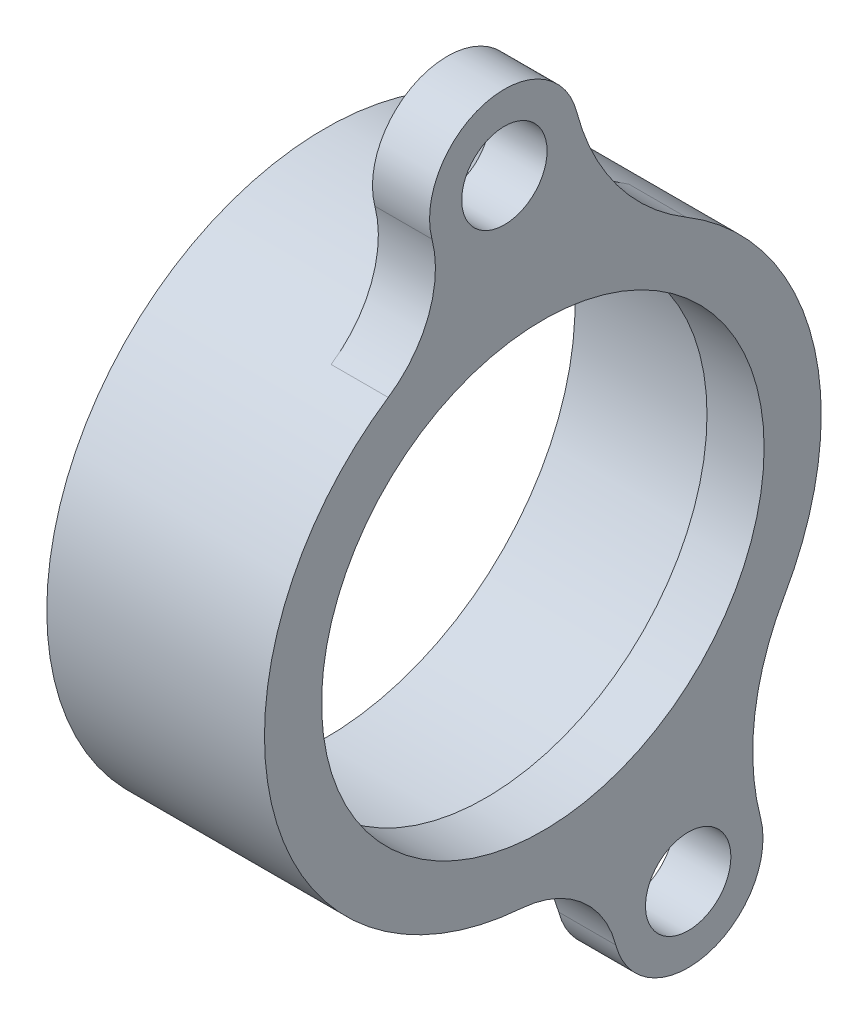
SolidWorks part; units mm, degrees
ref_plane "Front Plane" through (0, 0, 0) normal (0, 0, 1) x (1, 0, 0)
ref_plane "Top Plane" through (0, 0, 0) normal (0, 1, 0) x (1, 0, 0)
ref_plane "Right Plane" through (0, 0, 0) normal (1, 0, 0) x (0, 0, -1)
sketch "Sketch1" plane through (0, 0, 0) normal (0, 0, 1) x (1, 0, 0)
  line L0 (30.9563, 12.3825) -> (38.1, 12.3825)
  line L1 (38.1, 12.3825) -> (38.1, 11.1125)
  line L2 (38.1, 11.1125) -> (30.9563, 11.1125)
  line L4 (30.9563, 11.1125) -> (30.9563, 12.3825)
  line L5 (0, 0) -> (40.0174, 0) construction
  dimension "D1" = 1.27
  dimension "D2" = 7.1437
revolve "Revolve1" add sketch "Sketch1" angle 360 about L5
sketch "Sketch2" plane through (38.1, 0, 0) normal (1, 0, 0) x (0, 0, -1)
  line L0 (7.5709, -19.2497) -> (-3.6897, 23.8296) construction
  line L1 (-4.9307, 15.4199) -> (1.5078, 17.1029) construction
  line L2 (-11.2501, -2.9407) -> (11.2501, 2.9407) construction
  line L4 (-2.9246, 11.8422) -> (1.5091, 13.0012) construction
  line L5 (1.5091, 13.0012) -> (2.7223, 17.4204) construction
  line L6 (2.7223, 17.4204) -> (-0.4983, 20.6807) construction
  line L7 (-0.4983, 20.6807) -> (-4.932, 19.5217) construction
  line L8 (-4.932, 19.5217) -> (-6.1452, 15.1025) construction
  line L9 (-6.1452, 15.1025) -> (-2.9246, 11.8422) construction
  arc A0 (-6.8773, 10.297) -> (-0.9588, -12.3453) centre (0, 0) ccw
  circle A1 centre (0, 0) radius 12.3825 construction
  arc A7 (1.5078, 17.1029) -> (-4.9307, 15.4199) centre (-1.7114, 16.2614) ccw
  arc A8 (-6.8773, 10.297) -> (-4.9307, 15.4199) centre (-9.501, 14.2253) ccw
  arc A9 (1.5078, 17.1029) -> (6.3668, 10.6202) centre (11.8783, 19.8137) ccw
  circle A10 centre (0, 0) radius 9.8425
  circle A11 centre (0, 0) radius 11.1125 construction
  arc A12 (9.6843, -14.1774) -> (10.7495, -6.1462) centre (20.0548, -11.4666) cw
  arc A14 (9.6843, -14.1774) -> (3.2458, -15.8604) centre (6.465, -15.0189) cw
  arc A15 (-0.9588, -12.3453) -> (3.2458, -15.8604) centre (-1.3245, -17.055) cw
  arc A16 (10.7495, -6.1462) -> (6.3668, 10.6202) centre (0, 0) ccw
  circle A17 centre (-1.7114, 16.2614) radius 3.9688 construction
  arc A18 (1.5403, 20.0021) -> (-7.5172, 18.5996) centre (-2.9885, 19.3009) ccw construction
  arc A19 (7.5318, -19.9007) -> (7.5172, -18.5996) centre (2.9885, -19.3009) ccw construction
  dimension "D1" = 1.27
  dimension "D2" = 3.3274
  dimension "D3" = 7.9375
extrude "Boss-Extrude1" add sketch "Sketch2" along normal blind 2.54
hole_wizard "#6 Clearance Hole1" positions "Sketch3" profile "Sketch5" hole size "#6" standard "ANSI Inch" end condition up to next
sketch "Sketch3" plane through (40.64, 0, 0) normal (1, 0, 0) x (0, 0, -1)
  point P0 (-1.7114, 16.2614)
  point P3 (6.465, -15.0189)
sketch "Sketch5" plane through (40.64, 16.2614, 1.7114) normal (0, 1, 0) x (0, 0, -1)
  line L0 (0, 0) -> (0, 2.54)
  line L1 (0, 2.54) -> (1.8986, 2.54)
  line L2 (1.8986, 2.54) -> (1.8986, 0)
  line L5 (1.8986, 0) -> (0, 0)
  line L11 (0, -6.35) -> (0, 107.95) construction
  dimension "Thru Hole Dia." = 3.7973
  dimension "Thru Hole Depth" = 2.54
